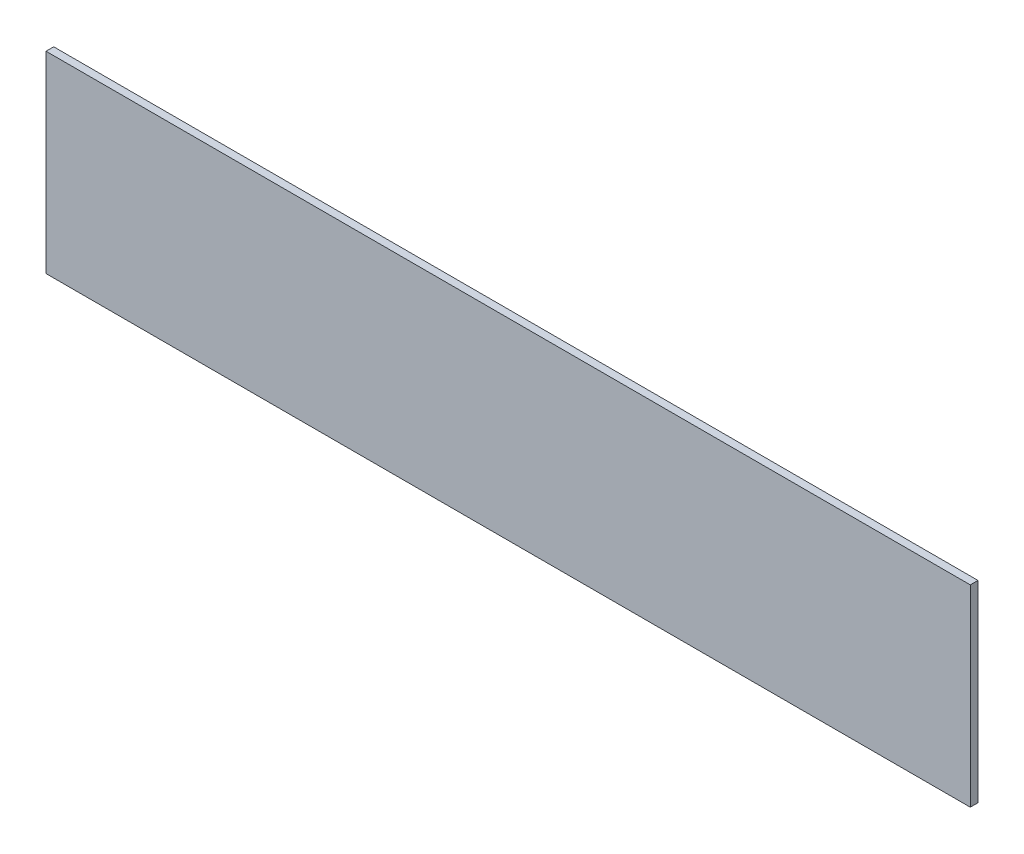
SolidWorks part; units mm, degrees
ref_plane "Ön Düzlem" through (0, 0, 0) normal (0, 0, 1) x (1, 0, 0)
ref_plane "Üst Düzlem" through (0, 0, 0) normal (0, 1, 0) x (1, 0, 0)
ref_plane "Sağ Düzlem" through (0, 0, 0) normal (1, 0, 0) x (0, 0, -1)
sketch "Çizim1" plane through (0, 0, 0) normal (0, 0, 1) x (1, 0, 0)
  line L1 (0, 0) -> (2400, 0)
  line L2 (0, 0) -> (0, -500)
  line L3 (0, -500) -> (2400, -500)
  line L4 (2400, 0) -> (2400, -500)
  dimension "D1" = 500
  dimension "D2" = 2400
base flange "Taban-Flanş1" sketch "Çizim1" thickness 20 reverse thickness direction no parameters "D1"=2.5
sketch "Büküm-Çizgileri1" [suppressed] plane through (0, 0, 0) normal (0, 1, 0) x (1, 0, 0)
sketch "Sınırlandırma-Kutusu1" [suppressed] plane through (0, 0, 0) normal (0, 1, 0) x (1, 0, 0)
sheet metal parameters "Sac-Levha1" thickness 20 parameters "D1"=2.5
flat pattern "Düz-Çoğaltma1" [suppressed]
sketch "Büküm-Çizgileri2" plane through (0, 0, 0) normal (0, 1, 0) x (1, 0, 0)
sketch3d "Sınırlandırma-Kutusu2" [suppressed]
  line L0 (0, -500, 0) -> (2400, -500, 0) construction
  line L1 (0, 0, 0) -> (2400, 0, 0) construction
  line L2 (0, -500, 0) -> (0, 0, 0) construction
  line L3 (2400, -500, 0) -> (2400, 0, 0) construction
